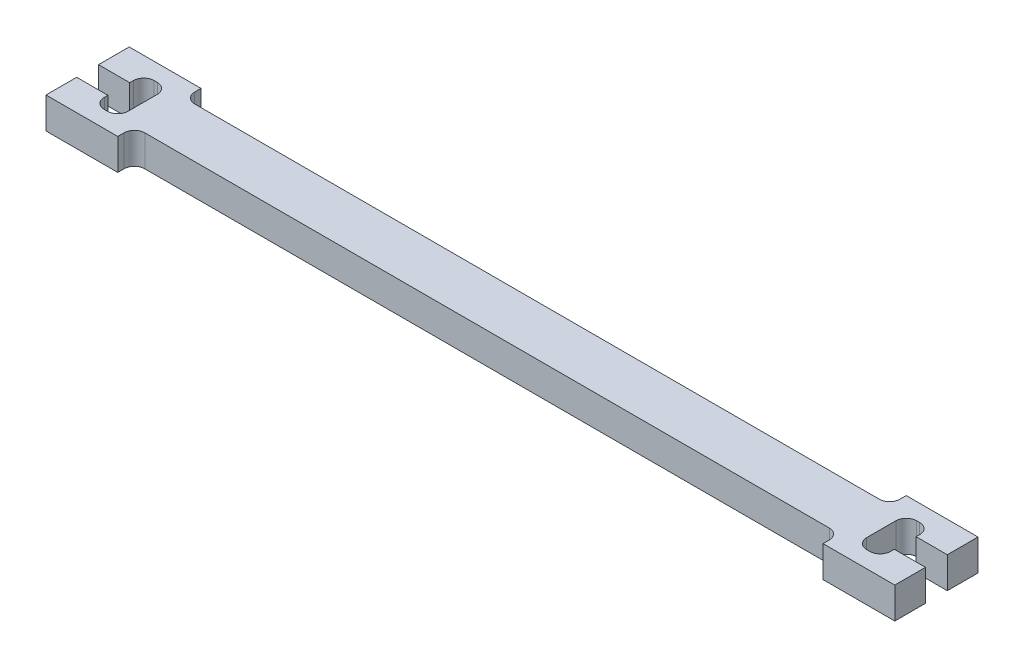
SolidWorks part; units mm, degrees
ref_plane "Front Plane" through (0, 0, 0) normal (0, 0, 1) x (1, 0, 0)
ref_plane "Top Plane" through (0, 0, 0) normal (0, 1, 0) x (1, 0, 0)
ref_plane "Right Plane" through (0, 0, 0) normal (1, 0, 0) x (0, 0, -1)
sketch "Sketch1" plane through (0, 0, 0) normal (0, 1, 0) x (1, 0, 0)
  line L0 (-40.8, 0) -> (40.8, 0) construction
  line L1 (-40.8, 4) -> (40.8, 4)
  line L2 (-40.8, 4) -> (-40.8, -4)
  line L3 (-40.8, -4) -> (40.8, -4)
  line L4 (40.8, 4) -> (40.8, -4)
  line L5 (-40.8, 4) -> (40.8, -4) construction
  line L6 (-40.8, -4) -> (40.8, 4) construction
  line L7 (-35.5, 2.4) -> (-35.5, 4) construction
  line L8 (-40.8, 1.05) -> (-37.8, 1.05)
  line L9 (-40.8, 1.05) -> (-40.8, -1.05)
  line L10 (-40.8, -1.05) -> (-37.8, -1.05)
  line L11 (-37.8, 1.05) -> (-37.8, -1.05)
  line L12 (-40.8, 1.05) -> (-37.8, -1.05) construction
  line L13 (-40.8, -1.05) -> (-37.8, 1.05) construction
  line L14 (-37.8, 2.4) -> (-35.5, 2.4)
  line L15 (-37.8, 2.4) -> (-37.8, -2.4)
  line L16 (-37.8, -2.4) -> (-35.5, -2.4)
  line L17 (-35.5, 2.4) -> (-35.5, -2.4)
  line L18 (-37.8, 2.4) -> (-35.5, -2.4) construction
  line L19 (-37.8, -2.4) -> (-35.5, 2.4) construction
  line L20 (-33.9, 2.4) -> (33.9, 2.4)
  line L21 (-33.9, 2.4) -> (-33.9, -2.4)
  line L22 (-33.9, -2.4) -> (33.9, -2.4)
  line L23 (33.9, 2.4) -> (33.9, -2.4)
  line L24 (-33.9, 2.4) -> (33.9, -2.4) construction
  line L25 (-33.9, -2.4) -> (33.9, 2.4) construction
  line L26 (-35.5, 2.4) -> (-33.9, 2.4) construction
  line L27 (-33.9, 2.4) -> (-33.9, 4)
  line L28 (-33.9, -2.4) -> (-33.9, -4)
  line L29 (0, 4) -> (0, -4) construction
  line L30 (33.9, -2.4) -> (33.9, -4)
  line L31 (-40.8, 4) -> (-40.8, -4)
  line L32 (40.8, 4) -> (40.8, -4)
  line L33 (33.9, 2.4) -> (33.9, 4)
  line L34 (40.8, -1.05) -> (37.8, -1.05)
  line L35 (37.8, -2.4) -> (35.5, -2.4)
  line L36 (35.5, 2.4) -> (35.5, -2.4)
  line L37 (37.8, 2.4) -> (35.5, 2.4)
  line L38 (37.8, 2.4) -> (37.8, -2.4)
  line L39 (40.8, 1.05) -> (37.8, 1.05)
  point P0 (0, 0)
  point P8 (-39.3, 0)
  point P13 (-36.65, 0)
  point P18 (0, 0)
  dimension "D1" = 8
  dimension "D2" = 81.6
  dimension "D3" = 3
  dimension "D4" = 2.3
  dimension "D5" = 4.8
  dimension "D6" = 2.1
extrude "Base shape" add sketch "Sketch1" along normal blind 3 contours L23 L20 L21 L22 | L28 L21 L27 L1 L2 L8 L15 L14 L17 L16 L10 L3 | L39 L4 L1 L33 L23 L30 L3 L32 L34 L38 L35 L36 L37 region at (-37.35, 0, -3.8944) region at (37.35, 0, -3.8944) region at (0, 0, 0)
fillet "Milling fillets" radius 1 12 edges at (37.8, 1.5, 2.4) (-35.5, 1.5, 2.4) (-37.8, 1.5, 2.4) (35.5, 1.5, 2.4) (35.5, 1.5, -2.4) (-37.8, 1.5, -2.4) (-35.5, 1.5, -2.4) (37.8, 1.5, -2.4) (33.9, 1.5, 2.4) (33.9, 1.5, -2.4) (-33.9, 1.5, -2.4) (-33.9, 1.5, 2.4)
sketch "Center axis sketch" plane through (40.8, 0, 0) normal (1, 0, 0) x (0, 0, -1)
  line L0 (-1.05, 0) -> (1.05, 3) construction
  point P4 (0, 1.5)
ref_axis "Center axis" through (-46.4653, 1.5, 0) along (1, 0, 0)
